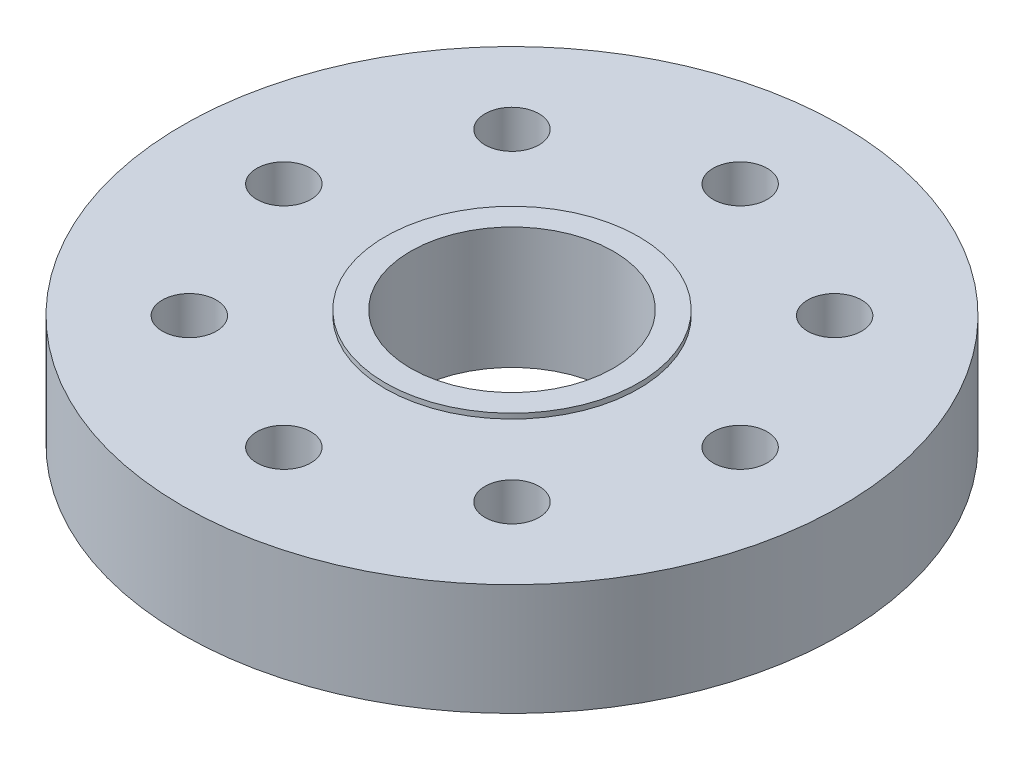
SolidWorks part; units mm, degrees
ref_plane "Alzado" through (0, 0, 0) normal (0, 0, 1) x (1, 0, 0)
ref_plane "Planta" through (0, 0, 0) normal (0, 1, 0) x (1, 0, 0)
ref_plane "Vista lateral" through (0, 0, 0) normal (1, 0, 0) x (0, 0, -1)
sketch "Croquis1" plane through (0, 0, 0) normal (0, 1, 0) x (1, 0, 0)
  line L0 (0, 0) -> (0, 9.75) construction
  line L1 (0, 9.75) -> (0, -9.75) construction
  line L2 (9.75, 0) -> (-9.75, 0) construction
  circle A0 centre (0, 0) radius 9.75
  circle A1 centre (0, 0) radius 3
  circle A2 centre (6.75, 0) radius 0.8
  circle A6 centre (0, -6.75) radius 0.8
  circle A7 centre (-6.75, 0) radius 0.8
  circle A8 centre (0, 6.75) radius 0.8
  circle A9 centre (0, 0) radius 3.75
  circle A10 centre (4.773, -4.773) radius 0.8
  circle A11 centre (0, -6.75) radius 0.8
  circle A12 centre (-4.773, -4.773) radius 0.8
  circle A13 centre (-6.75, 0) radius 0.8
  circle A14 centre (-4.773, 4.773) radius 0.8
  circle A15 centre (0, 6.75) radius 0.8
  circle A16 centre (4.773, 4.773) radius 0.8
  point P19 (0, 0)
  point P34 (0, 0)
  dimension "D1" = 19.5
  dimension "D2" = 6
  dimension "D3" = 6.75
  dimension "D4" = 1.6
  dimension "D5" = 4
  dimension "D6" = 7.5
extrude "Saliente-Extruir1" add sketch "Croquis1" along normal mid plane 3.3 contours A0 A9 A8 A7 A6 A2 | A9 A1 region at (-9.4742, 0, 0) region at (-3.6439, 0, 0)
extrude "Saliente-Extruir2" add sketch "Croquis1<3>" along normal mid plane 3.6 contours A9 A1 region at (-3.6439, 0, 0)
sketch "Croquis1<3>" plane through (0, 0, 0) normal (0, 1, 0) x (1, 0, 0) same geometry as "Croquis1"
sketch "Croquis2" plane through (0, -1.65, 0) normal (0, -1, 0) x (1, 0, 0)
  circle A2 centre (0, 0) radius 8.55
  circle A3 centre (0, 0) radius 8.55
  circle A4 centre (6.75, 0) radius 2
  circle A5 centre (4.5962, -4.5962) radius 2
  circle A6 centre (-0.1768, -6.3232) radius 2
  circle A7 centre (-4.773, -4.1694) radius 2
  circle A8 centre (-6.5, 0.6036) radius 2
  circle A9 centre (-4.3462, 5.1997) radius 2
  circle A10 centre (0.4268, 6.9268) radius 2
  circle A11 centre (5.023, 4.773) radius 2
  circle A12 centre (0, 0) radius 4.4
  circle A14 centre (0, 0) radius 2.5
  point P24 (0.125, 0.3018)
  dimension "D2" = 8
  dimension "D3" = 4
  dimension "D4" = 8.8
  dimension "D6" = 5
  dimension "D1" = 1.2
extrude "Cortar-Extruir3" cut sketch "Croquis2" against normal blind 1.8 contours A3 A12 A11 A10 A9 A8 A7 A6 A5 A4 region at (4.5088, -1.65, 0)
sketch "Croquis3" plane through (0, -1.65, 0) normal (0, -1, 0) x (1, 0, 0)
  circle A1 centre (0, 0) radius 3
  circle A2 centre (0, 0) radius 4.4
extrude "Saliente-Extruir3" add sketch "Croquis3" along normal blind 0.15
